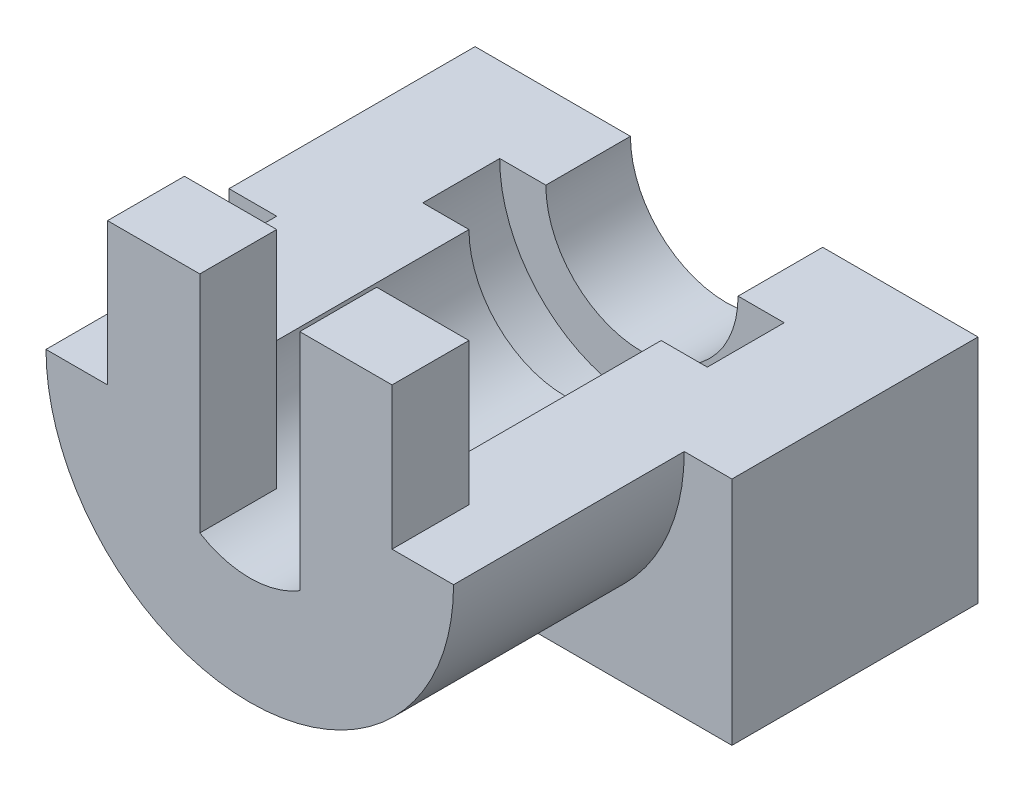
SolidWorks part; units mm, degrees
note: The reader was unsure of these and kept them because the rebuilt part matched: shared geometry of "草图1<4>".
ref_plane "前视基准面" through (0, 0, 0) normal (0, 0, 1) x (1, 0, 0)
ref_plane "上视基准面" through (0, 0, 0) normal (0, 1, 0) x (1, 0, 0)
ref_plane "右视基准面" through (0, 0, 0) normal (1, 0, 0) x (0, 0, -1)
sketch "草图1" plane through (0, 0, 0) normal (0, 0, 1) x (1, 0, 0)
  line L0 (-3.25, 9.25) -> (-3.25, -9.25)
  line L1 (-9.25, 9.25) -> (9.25, 9.25)
  line L2 (-9.25, 9.25) -> (-9.25, -9.25)
  line L3 (-9.25, -9.25) -> (9.25, -9.25)
  line L4 (9.25, 9.25) -> (9.25, -9.25)
  line L5 (-9.25, 9.25) -> (9.25, -9.25) construction
  line L6 (-9.25, -9.25) -> (9.25, 9.25) construction
  line L7 (0, 0) -> (-3.25, 0)
  line L8 (0, -1000) -> (0, 49000) construction
  line L9 (3.25, 9.25) -> (3.25, -9.25)
  line L10 (-6.25, 9.25) -> (-6.25, -9.25)
  line L11 (6.25, 9.25) -> (6.25, -9.25)
  line L12 (-9.25, -6.8191) -> (-6.25, -6.8191)
  line L13 (9.25, -6.8191) -> (6.25, -6.8191)
  line L14 (-9.25, 6.8191) -> (-6.25, 6.8191)
  line L15 (9.25, 6.8191) -> (6.25, 6.8191)
  line L16 (-1000, 0) -> (49000, 0)
  circle A0 centre (0, 0) radius 6.25
  circle A1 centre (0, 0) radius 9.25
  dimension "D1" = 12.5
  dimension "D3" = 3.25
  dimension "D2" = 3
extrude "凸台-拉伸1" add sketch "草图1" along normal blind 5 contours L0 A0 | L9 A0 | L10 A1 L0 A0 | L9 A1 L11 A0 | L0 A1 L10 A0 | L11 A1 L9 A0 | L0 A1 L9 A0 | A1 L10 L1 L2 | A1 L0 L1 L10 | A1 L11 L1 L9 | A1 L4 L1 L11 | A1 L14 L2 | A1 L4 L15 | L10 A1 L16 | L16 A1 L11 | L16 A1 L10 | L0 A0 L16 | L11 A1 L16 | L9 A0 L16
extrude "凸台-拉伸3" add sketch "草图1<4>" against normal blind 10 contours L10 A1 L0 A0 | L0 A1 L9 A0 | L9 A1 L11 A0 | L11 A1 L16 | L16 A1 L10
sketch "草图1<4>" plane through (0, 0, 0) normal (0, 0, 1) x (1, 0, 0) same geometry as "草图1"
sketch "草图2" plane through (0, 0, -10) normal (0, 0, -1) x (-1, 0, 0)
  line L0 (-1000, 0) -> (49000, 0)
  line L1 (-16.35, 15) -> (16.35, 15)
  line L2 (-16.35, 15) -> (-16.35, -15)
  line L3 (-16.35, -15) -> (16.35, -15)
  line L4 (16.35, 15) -> (16.35, -15)
  line L5 (-16.35, 15) -> (16.35, -15) construction
  line L6 (-16.35, -15) -> (16.35, 15) construction
  point P0 (0, 0)
  arc M8 (-9.25, 0) -> (9.25, 0) centre (0, 0) ccw
  dimension "D1" = 32.7
  dimension "D2" = 30
extrude "凸台-拉伸4" add sketch "草图2" along normal blind 10.5 contours L4 L0 L2 L3 M8
sketch "草图5" plane through (0, 0, -10) normal (0, 0, 1) x (1, 0, 0)
  line L0 (-9.25, 0) -> (-13.25, 0)
  line L1 (9.25, 0) -> (13.25, 0)
  arc A0 (-9.25, 0) -> (9.25, 0) centre (0, 0) ccw construction
  arc A1 (-9.25, 0) -> (9.25, 0) centre (0, 0) ccw
  circle A2 centre (0, 0) radius 13.25
  line M4 (16.35, 0) -> (9.25, 0)
  arc M5 (9.25, 0) -> (-9.25, 0) centre (0, 0) cw
  line M6 (-9.25, 0) -> (-16.35, 0)
  dimension "D1" = 4
extrude "凸台-拉伸6" add sketch "草图5" along normal up to surface (15 mm away) contours A2 M6 M4 M5
sketch "草图6" plane through (0, 0, -10) normal (0, 0, -1) x (-1, 0, 0)
  line L0 (9.25, 0) -> (6.25, 0) construction
  line L1 (-6.25, 0) -> (-9.25, 0) construction
  line L2 (9.25, 0) -> (6.25, 0)
  line L3 (-6.25, 0) -> (-9.25, 0)
  arc A0 (-9.25, 0) -> (9.25, 0) centre (0, 0) ccw construction
  arc A1 (-6.25, 0) -> (6.25, 0) centre (0, 0) ccw construction
  arc A2 (-9.25, 0) -> (9.25, 0) centre (0, 0) ccw
  arc A3 (-6.25, 0) -> (6.25, 0) centre (0, 0) ccw
extrude "凸台-拉伸7" add sketch "草图6" along normal blind 5.5
sketch "草图7" plane through (0, 0, -20.5) normal (0, 0, -1) x (-1, 0, 0)
  line L0 (16.35, 0) -> (16.35, -15) construction
  line L1 (-16.35, -15) -> (16.35, -15) construction
  line L2 (-16.35, 0) -> (-16.35, -15) construction
  line L3 (16.35, 0) -> (16.35, -15)
  line L4 (-16.35, -15) -> (16.35, -15)
  line L5 (-16.35, 0) -> (-16.35, -15)
  line L6 (-16.35, 0) -> (-6.25, 0)
  line L7 (6.25, 0) -> (16.35, 0)
  arc A0 (-6.25, 0) -> (6.25, 0) centre (0, 0) ccw construction
  arc A1 (-6.25, 0) -> (6.25, 0) centre (0, 0) ccw
extrude "凸台-拉伸8" add sketch "草图7" along normal blind 5.5
sketch "草图9" plane through (0, 0, 0) normal (0, 1, 0) x (1, 0, 0)
  line L0 (0, -1000) -> (0, 49000) construction
  line L1 (-9.25, 20.5) -> (9.25, 20.5) construction
  line L2 (-9.25, 20.5) -> (9.25, 20.5)
  line L3 (-9.25, 20.5) -> (-9.25, 15.5)
  line L4 (-9.25, 15.5) -> (9.25, 15.5)
  line L5 (9.25, 20.5) -> (9.25, 15.5)
  line L6 (-9.25, 20.5) -> (9.25, 15.5) construction
  line L7 (-9.25, 15.5) -> (9.25, 20.5) construction
  line L8 (9.25, 15.5) -> (-9.25, 15.5) construction
  line L9 (-9.25, 20.5) -> (-9.25, 15.5) construction
  line L10 (-12.25, 23.5) -> (12.25, 23.5)
  line L11 (12.25, 23.5) -> (12.25, 12.5)
  line L12 (-12.25, 12.5) -> (12.25, 12.5)
  line L13 (-12.25, 23.5) -> (-12.25, 12.5)
  line L14 (-16.35, 26) -> (-16.35, 10) construction
  circle A0 centre (-12.25, 8.5779) radius 3.25
  point P1 (0, 18)
  point P22 (-12.25, 8.5779)
  dimension "D4" = 6.5
  dimension "D2" = 4.1
  dimension "D3" = 7.1
  dimension "D1" = 3
